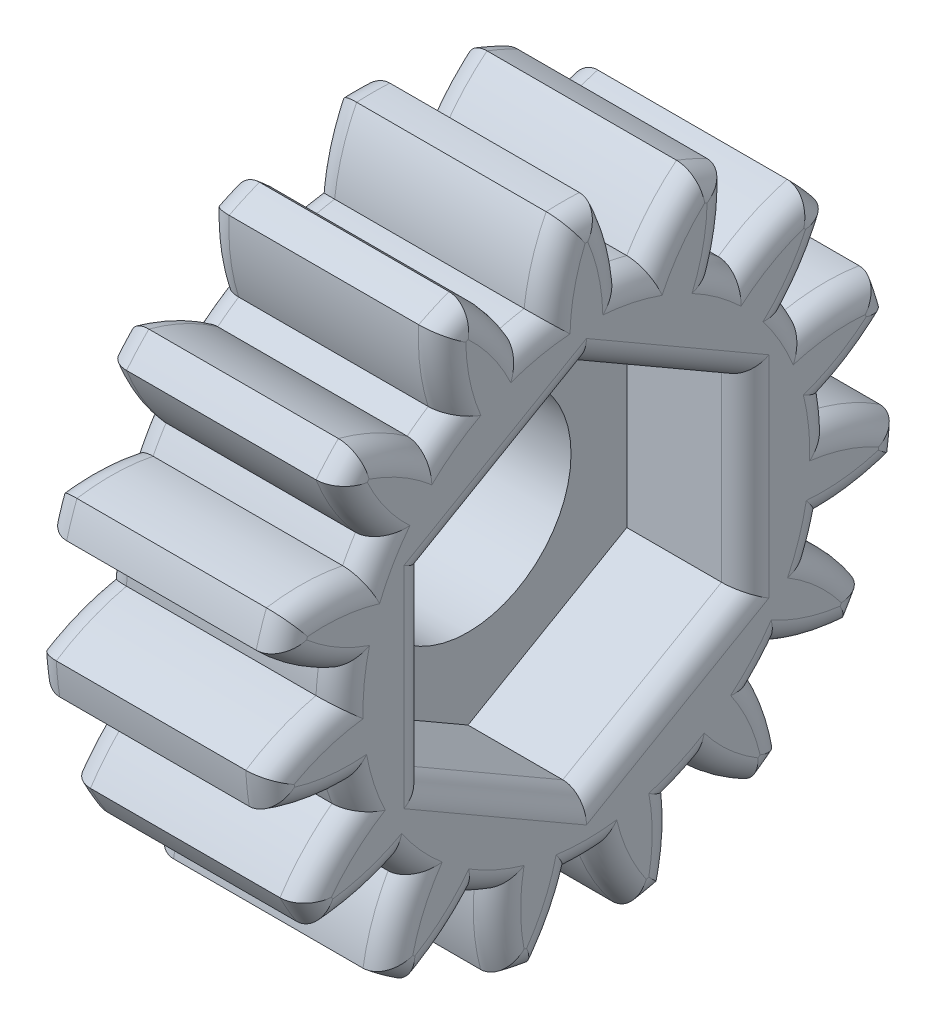
SolidWorks part; units mm, degrees
ref_plane "Alzado" through (0, 0, 0) normal (0, 0, 1) x (1, 0, 0)
ref_plane "Planta" through (0, 0, 0) normal (0, 1, 0) x (1, 0, 0)
ref_plane "Vista lateral" through (0, 0, 0) normal (1, 0, 0) x (0, 0, -1)
sketch "Croquis1" plane through (0, 0, 0) normal (1, 0, 0) x (0, 0, -1)
  line L1 (0, -7.74) -> (6.703, -3.87)
  line L2 (6.703, -3.87) -> (6.703, 3.87)
  line L3 (6.703, 3.87) -> (0, 7.74)
  line L4 (0, 7.74) -> (-6.703, 3.87)
  line L5 (-6.703, 3.87) -> (-6.703, -3.87)
  line L6 (-6.703, -3.87) -> (0, -7.74)
  arc A0 (-10.3033, 1.6319) -> (-10.4175, 0.546) centre (0, 0) ccw
  arc A1 (-10.4175, 0.546) -> (-13.3816, -0.7013) centre (-8.4189, -8.3496) ccw
  arc A2 (-13.3816, -0.7013) -> (-13.235, -2.0962) centre (0, 0) ccw
  arc A3 (-13.235, -2.0962) -> (-10.0763, -2.6999) centre (-9.9709, 6.4168) ccw
  circle A4 centre (0, 0) radius 4.35
  arc A5 (-8.7488, 5.6815) -> (-9.2948, 4.7359) centre (0, 0) ccw
  arc A6 (-9.2948, 4.7359) -> (-12.51, 4.8021) centre (-11.0871, -4.2035) ccw
  arc A7 (-12.51, 4.8021) -> (-12.9434, 3.4682) centre (0, 0) ccw
  arc A8 (-12.9434, 3.4682) -> (-10.3033, 1.6319) centre (-6.499, 9.9175) ccw
  arc A9 (-5.6815, 8.7488) -> (-6.5649, 8.107) centre (0, 0) ccw
  arc A10 (-6.5649, 8.107) -> (-9.4752, 9.4752) centre (-11.8383, 0.6695) ccw
  arc A11 (-9.4752, 9.4752) -> (-10.4138, 8.4329) centre (0, 0) ccw
  arc A12 (-10.4138, 8.4329) -> (-8.7488, 5.6815) centre (-1.9033, 11.7035) ccw
  arc A13 (-1.6319, 10.3033) -> (-2.6999, 10.0763) centre (0, 0) ccw
  arc A14 (-2.6999, 10.0763) -> (-4.8021, 12.51) centre (-10.5425, 5.4267) ccw
  arc A15 (-4.8021, 12.51) -> (-6.0835, 11.9395) centre (0, 0) ccw
  arc A16 (-6.0835, 11.9395) -> (-5.6815, 8.7488) centre (3.0215, 11.4658) ccw
  arc A17 (2.6999, 10.0763) -> (1.6319, 10.3033) centre (0, 0) ccw
  arc A18 (1.6319, 10.3033) -> (0.7013, 13.3816) centre (-7.4239, 9.2456) ccw
  arc A19 (0.7013, 13.3816) -> (-0.7013, 13.3816) centre (0, 0) ccw
  arc A20 (-0.7013, 13.3816) -> (-1.6319, 10.3033) centre (7.4239, 9.2456) ccw
  arc A21 (6.5649, 8.107) -> (5.6815, 8.7488) centre (0, 0) ccw
  arc A22 (5.6815, 8.7488) -> (6.0835, 11.9395) centre (-3.0215, 11.4658) ccw
  arc A23 (6.0835, 11.9395) -> (4.8021, 12.51) centre (0, 0) ccw
  arc A24 (4.8021, 12.51) -> (2.6999, 10.0763) centre (10.5425, 5.4267) ccw
  arc A25 (9.2948, 4.7359) -> (8.7488, 5.6815) centre (0, 0) ccw
  arc A26 (8.7488, 5.6815) -> (10.4138, 8.4329) centre (1.9033, 11.7035) ccw
  arc A27 (10.4138, 8.4329) -> (9.4752, 9.4752) centre (0, 0) ccw
  arc A28 (9.4752, 9.4752) -> (6.5649, 8.107) centre (11.8383, 0.6695) ccw
  arc A29 (10.4175, 0.546) -> (10.3033, 1.6319) centre (0, 0) ccw
  arc A30 (10.3033, 1.6319) -> (12.9434, 3.4682) centre (6.499, 9.9175) ccw
  arc A31 (12.9434, 3.4682) -> (12.51, 4.8021) centre (0, 0) ccw
  arc A32 (12.51, 4.8021) -> (9.2948, 4.7359) centre (11.0871, -4.2035) ccw
  arc A33 (9.7389, -3.7384) -> (10.0763, -2.6999) centre (0, 0) ccw
  arc A34 (10.0763, -2.6999) -> (13.235, -2.0962) centre (9.9709, 6.4168) ccw
  arc A35 (13.235, -2.0962) -> (13.3816, -0.7013) centre (0, 0) ccw
  arc A36 (13.3816, -0.7013) -> (10.4175, 0.546) centre (8.4189, -8.3496) ccw
  arc A37 (7.3764, -7.3764) -> (8.107, -6.5649) centre (0, 0) ccw
  arc A38 (8.107, -6.5649) -> (11.2382, -7.2982) centre (11.7188, 1.8065) ccw
  arc A39 (11.2382, -7.2982) -> (11.9395, -6.0835) centre (0, 0) ccw
  arc A40 (11.9395, -6.0835) -> (9.7389, -3.7384) centre (4.295, -11.052) ccw
  arc A41 (3.7384, -9.7389) -> (4.7359, -9.2948) centre (0, 0) ccw
  arc A42 (4.7359, -9.2948) -> (7.2982, -11.2382) centre (11.4404, -3.1162) ccw
  arc A43 (7.2982, -11.2382) -> (8.4329, -10.4138) centre (0, 0) ccw
  arc A44 (8.4329, -10.4138) -> (7.3764, -7.3764) centre (-0.5716, -11.8435) ccw
  arc A45 (-0.546, -10.4175) -> (0.546, -10.4175) centre (0, 0) ccw
  arc A46 (0.546, -10.4175) -> (2.0962, -13.235) centre (9.1839, -7.5) ccw
  arc A47 (2.0962, -13.235) -> (3.4682, -12.9434) centre (0, 0) ccw
  arc A48 (3.4682, -12.9434) -> (3.7384, -9.7389) centre (-5.3394, -10.587) ccw
  arc A49 (-4.7359, -9.2948) -> (-3.7384, -9.7389) centre (0, 0) ccw
  arc A50 (-3.7384, -9.7389) -> (-3.4682, -12.9434) centre (5.3394, -10.587) ccw
  arc A51 (-3.4682, -12.9434) -> (-2.0962, -13.235) centre (0, 0) ccw
  arc A52 (-2.0962, -13.235) -> (-0.546, -10.4175) centre (-9.1839, -7.5) ccw
  arc A53 (-8.107, -6.5649) -> (-7.3764, -7.3764) centre (0, 0) ccw
  arc A54 (-7.3764, -7.3764) -> (-8.4329, -10.4138) centre (0.5716, -11.8435) ccw
  arc A55 (-8.4329, -10.4138) -> (-7.2982, -11.2382) centre (0, 0) ccw
  arc A56 (-7.2982, -11.2382) -> (-4.7359, -9.2948) centre (-11.4404, -3.1162) ccw
  arc A57 (-10.0763, -2.6999) -> (-9.7389, -3.7384) centre (0, 0) ccw
  arc A58 (-9.7389, -3.7384) -> (-11.9395, -6.0835) centre (-4.295, -11.052) ccw
  arc A59 (-11.9395, -6.0835) -> (-11.2382, -7.2982) centre (0, 0) ccw
  arc A60 (-11.2382, -7.2982) -> (-8.107, -6.5649) centre (-11.7188, 1.8065) ccw
  circle A61 centre (0, 0) radius 6.703 construction
  point P111 (0, 0)
  dimension "D1" = 8.7
  dimension "D2" = 10.4317
  dimension "D3" = 9.1173
  dimension "D4" = 13.4
  dimension "D5" = 7.74
  dimension "D6" = 9.9709
  dimension "D7" = 10.0763
  dimension "D10" = 15
extrude "Saliente-Extruir1" add sketch "Croquis1" against normal blind 10 contours A16 A9 A10 A11 A12 A5 A6 A7 A8 A0 A1 A2 A3 A57 A58 A59 A60 A53 A54 A55 A56 A49 A50 A51 A52 A45 A46 A47 A48 A41 A42 A43 A44 A37 A38 A39 A40 A33 A34 A35 A36 A29 A30 A31 A32 A25 A26 A27 A28 A21 A22 A23 A24 A17 A18 A19 A20 A13 A14 A15
extrude "Cortar-Extruir1" cut sketch "Croquis1<3>" against normal blind 5 contours L5 L6 L1 L2 L3 L4 A4 | A4 region at (0, -5.6277, 3.2491) region at (0, 0, 0)
sketch "Croquis1<3>" plane through (0, 0, 0) normal (1, 0, 0) x (0, 0, -1) same geometry as "Croquis1"
extrude "Cortar-Extruir2" cut sketch "Croquis1<4>" against normal through all contours A4 region at (0, 0, 0)
sketch "Croquis1<4>" plane through (0, 0, 0) normal (1, 0, 0) x (0, 0, -1) same geometry as "Croquis1"
fillet "Redondeo1" radius 1 127 edges at (-10, 10.3263, 6.0243) (-10, 8.4395, 6.1316) (-10, 8.9204, 7.9593) (-10, 8.9664, 9.9581) (-10, 6.9832, 9.7035) (-10, 5.2159, 9.0342) (-10, 4.9119, 10.8994) (-10, 4.1408, 12.7442) (-10, 2.4327, 11.705) (-10, 1.0904, 10.3746) (-10, 0.0541, 11.955) (-10, -1.4007, 13.3266) (-10, -2.5384, 11.6825) (-10, -3.2236, 9.9212) (-10, -4.8131, 10.9434) (-10, -6.7, 11.6047) (-10, -7.0707, 9.64) (-10, -6.9802, 7.7523) (-10, -8.8481, 8.0396) (-10, -10.8408, 7.8763) (-10, -10.3803, 5.9307) (-10, -9.5299, 4.243) (-10, -11.3532, 3.7457) (-10, -13.1072, 2.786) (-10, -11.8951, 1.1959) (-10, -10.4317, 0) (-10, -11.8951, -1.1959) (-10, -13.1072, -2.786) (-10, -11.3532, -3.7457) (-10, -9.5299, -4.243) (-10, -10.3803, -5.9307) (-10, -10.8408, -7.8763) (-10, -8.8481, -8.0396) (-10, -6.9802, -7.7523) (-10, -7.0707, -9.64) (-10, -6.7, -11.6047) (-10, -4.8131, -10.9434) (-10, -3.2236, -9.9212) (-10, -2.5384, -11.6825) (-10, -1.4007, -13.3266) (-10, 0.0541, -11.955) (-10, 1.0904, -10.3746) (-10, 2.4327, -11.705) (-10, 4.1408, -12.7442) (-10, 4.9119, -10.8994) (-10, 5.2159, -9.0342) (-10, 6.9832, -9.7035) (-10, 8.9664, -9.9581) (-10, 8.9204, -7.9593) (-10, 8.4395, -6.1316) (-10, 10.3263, -6.0243) (-10, 12.2415, -5.4503) (-10, 11.3866, -3.6429) (-10, 10.2038, -2.1689) (-10, 11.8838, -1.3034) (-10, 13.4, 0) (-10, 11.8838, 1.3034) (-10, 10.2038, 2.1689) (-10, 11.3866, 3.6429) (-10, 12.2415, 5.4503) (-10, 0, -4.35) (0, 11.3866, 3.6429) (0, 10.2038, 2.1689) (0, 11.8838, 1.3034) (0, 13.4, 0) (0, 11.8838, -1.3034) (0, 10.2038, -2.1689) (0, 11.3866, -3.6429) (0, 12.2415, -5.4503) (0, 10.3263, -6.0243) (0, 8.4395, -6.1316) (0, 8.9204, -7.9593) (0, 8.9664, -9.9581) (0, 6.9832, -9.7035) (0, 5.2159, -9.0342) (0, 4.9119, -10.8994) (0, 4.1408, -12.7442) (0, 2.4327, -11.705) (0, 1.0904, -10.3746) (0, 0.0541, -11.955) (0, -1.4007, -13.3266) (0, -2.5384, -11.6825) (0, -3.2236, -9.9212) (0, -4.8131, -10.9434) (0, -6.7, -11.6047) (0, -7.0707, -9.64) (0, -6.9802, -7.7523) (0, -8.8481, -8.0396) (0, -10.8408, -7.8763) (0, -10.3803, -5.9307) (0, -9.5299, -4.243) (0, -11.3532, -3.7457) (0, -13.1072, -2.786) (0, -11.8951, -1.1959) (0, -10.4317, 0) (0, -11.8951, 1.1959) (0, -13.1072, 2.786) (0, -11.3532, 3.7457) (0, -9.5299, 4.243) (0, -10.3803, 5.9307) (0, -10.8408, 7.8763) (0, -8.8481, 8.0396) (0, -6.9802, 7.7523) (0, -7.0707, 9.64) (0, -6.7, 11.6047) (0, -4.8131, 10.9434) (0, -3.2236, 9.9212) (0, -2.5384, 11.6825) (0, -1.4007, 13.3266) (0, 0.0541, 11.955) (0, 1.0904, 10.3746) (0, 2.4327, 11.705) (0, 4.1408, 12.7442) (0, 4.9119, 10.8994) (0, 5.2159, 9.0342) (0, 6.9832, 9.7035) (0, 8.9664, 9.9581) (0, 8.9204, 7.9593) (0, 8.4395, 6.1316) (0, 10.3263, 6.0243) (0, 12.2415, 5.4503) (0, -5.805, 3.3515) (0, -5.805, -3.3515) (0, 0, -6.703) (0, 5.805, -3.3515) (0, 5.805, 3.3515) (0, 0, 6.703)
